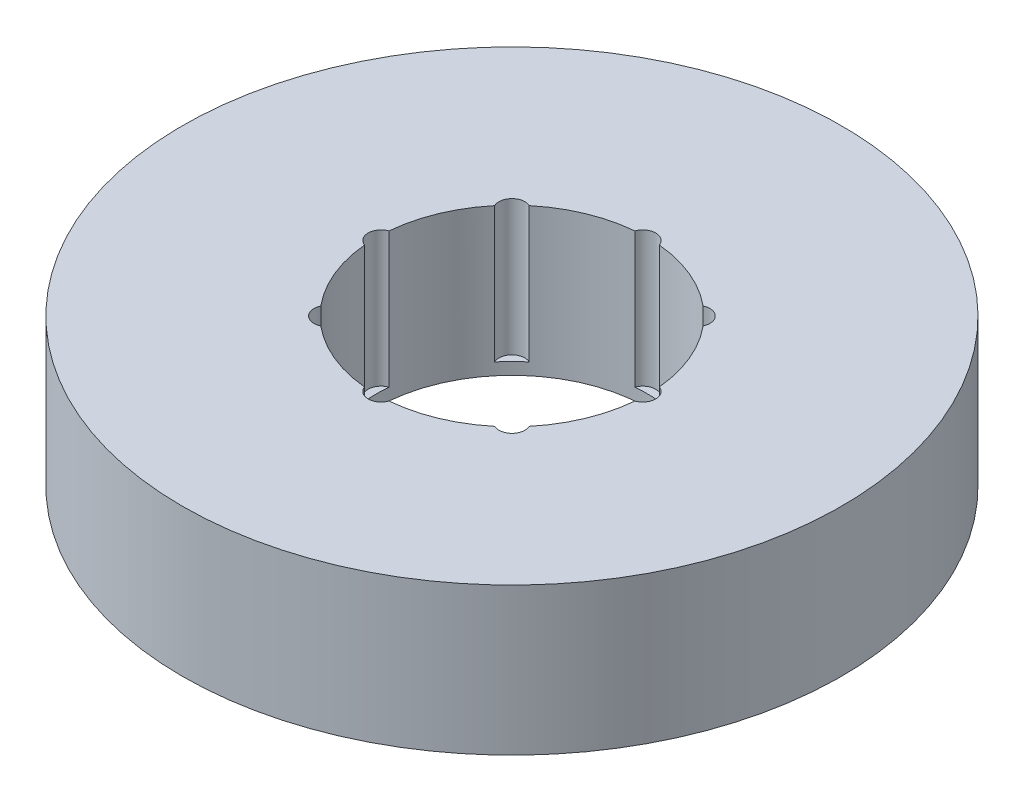
SolidWorks part; units mm, degrees
ref_plane "Front Plane" through (0, 0, 0) normal (0, 0, 1) x (1, 0, 0)
ref_plane "Top Plane" through (0, 0, 0) normal (0, 1, 0) x (1, 0, 0)
ref_plane "Right Plane" through (0, 0, 0) normal (1, 0, 0) x (0, 0, -1)
sketch "Sketch1" plane through (0, 0, 0) normal (0, 1, 0) x (1, 0, 0)
  circle A0 centre (0, 0) radius 42.5
  dimension "FLANGE_OD" = 85
extrude "Boss-Extrude1" add sketch "Sketch1" along normal blind 19
sketch "Sketch2" plane through (0, 0, 0) normal (0, 1, 0) x (1, 0, 0)
  circle A0 centre (0, 0) radius 17.5
  dimension "BORE_D" = 35
extrude "Cut-Extrude1" cut sketch "Sketch2" along normal through all
sketch "Sketch3" plane through (0, 19, 0) normal (0, 1, 0) x (1, 0, 0)
  circle A0 centre (0, 0) radius 16.8718 construction
  circle A1 centre (-16.8718, 0) radius 1.6698
  dimension "BOLT_D" = 3.3397
  dimension "BOLT_PCD" = 33.7436
extrude "Cut-Extrude2" cut sketch "Sketch3" against normal blind 17.454
pattern_circular "CirPattern1" count 8 over 360 about axis through (0, 0, 0) along (0, 1, 0) of "Cut-Extrude2"
